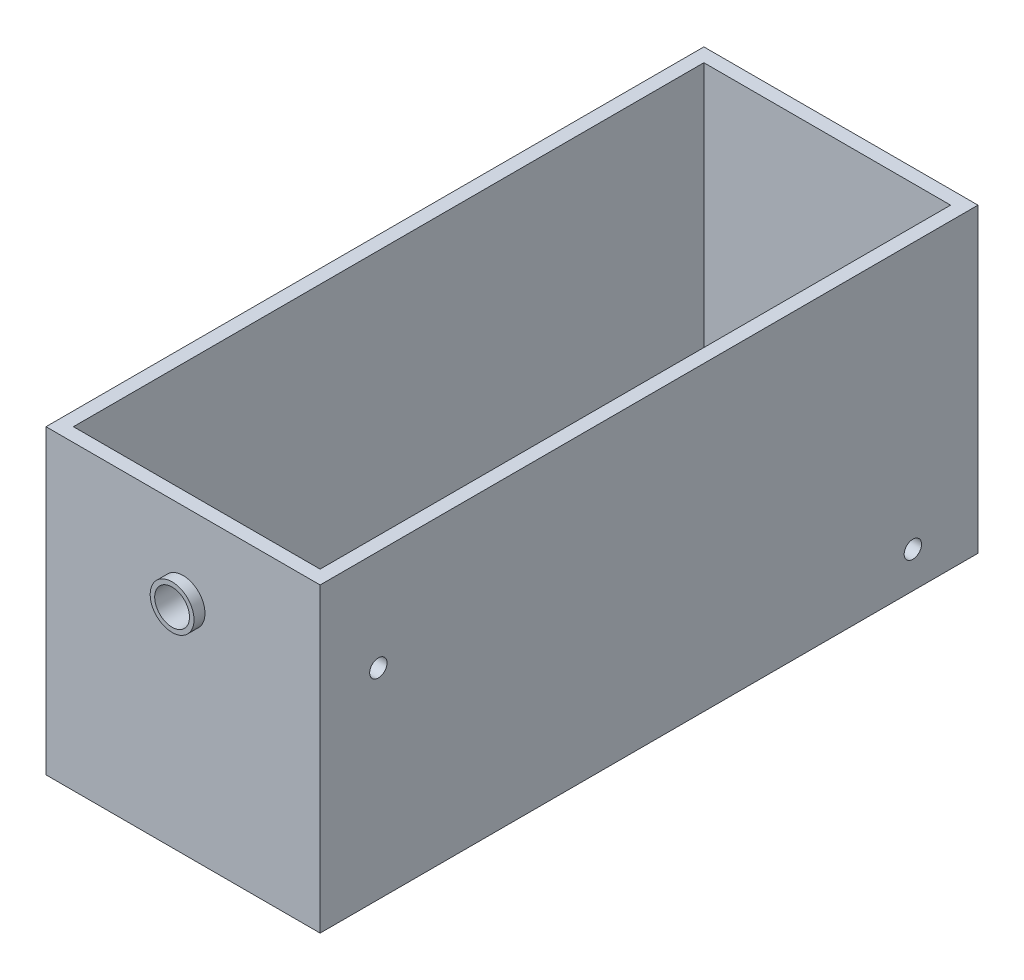
SolidWorks part; units mm, degrees
ref_plane "Front Plane" through (0, 0, 0) normal (0, 0, 1) x (1, 0, 0)
ref_plane "Top Plane" through (0, 0, 0) normal (0, 1, 0) x (1, 0, 0)
ref_plane "Right Plane" through (0, 0, 0) normal (1, 0, 0) x (0, 0, -1)
sketch "Sketch1" plane through (0, 0, 0) normal (0, 1, 0) x (1, 0, 0)
  line L1 (-25, -60) -> (25, -60)
  line L2 (-25, -60) -> (-25, 60)
  line L3 (-25, 60) -> (25, 60)
  line L4 (25, -60) -> (25, 60)
  line L5 (-25, -60) -> (25, 60) construction
  line L6 (-25, 60) -> (25, -60) construction
  point P0 (0, 0)
  dimension "D1" = 120
  dimension "D2" = 50
extrude "Boss-Extrude1" add sketch "Sketch1" along normal blind 5
sketch "Sketch2" plane through (0, 5, 0) normal (0, 1, 0) x (1, 0, 0)
  line L1 (-22.5, -57.5) -> (22.5, -57.5)
  line L2 (-22.5, -57.5) -> (-22.5, 57.5)
  line L3 (-22.5, 57.5) -> (22.5, 57.5)
  line L4 (22.5, -57.5) -> (22.5, 57.5)
  line L5 (-22.5, -57.5) -> (22.5, 57.5) construction
  line L6 (-22.5, 57.5) -> (22.5, -57.5) construction
  line L7 (-25, 60) -> (25, 60)
  line L8 (-25, 60) -> (-25, -60)
  line L9 (-25, -60) -> (25, -60)
  line L10 (25, 60) -> (25, -60)
  line L11 (-25, 60) -> (25, -60) construction
  line L12 (-25, -60) -> (25, 60) construction
  point P0 (0, 0)
  point P6 (0, 0)
  dimension "D1" = 45
  dimension "D2" = 115
extrude "Boss-Extrude2" add sketch "Sketch2" along normal blind 50
sketch "Sketch3" plane through (0, 0, 60) normal (0, 0, 1) x (1, 0, 0)
  line L0 (-25, 55) -> (25, 55) construction
  circle A0 centre (0, 40) radius 3.175
  dimension "D2" = 6.35
  dimension "D1" = 15
extrude "Cut-Extrude1" cut sketch "Sketch3" against normal blind 50
sketch "Sketch4" plane through (0, 0, 60) normal (0, 0, 1) x (1, 0, 0)
  circle A0 centre (0, 40) radius 3.175
  circle A1 centre (0, 40) radius 4
  dimension "D1" = 8
extrude "Boss-Extrude3" add sketch "Sketch4" along normal blind 2
sketch "Sketch5" plane through (0, 0, -60) normal (0, 0, -1) x (-1, 0, 0)
  line L0 (-25, 0) -> (25, 0) construction
  circle A0 centre (0, 10) radius 3.175
  dimension "D2" = 6.35
  dimension "D1" = 10
extrude "Cut-Extrude2" cut sketch "Sketch5" against normal blind 14
sketch "Sketch6" plane through (0, 0, -60) normal (0, 0, -1) x (-1, 0, 0)
  circle A0 centre (0, 10) radius 3.175
  circle A1 centre (0, 10) radius 4
  dimension "D1" = 8
extrude "Boss-Extrude4" add sketch "Sketch6" along normal blind 2
sketch "Sketch7" plane through (25, 0, 0) normal (1, 0, 0) x (0, 0, -1)
  circle A0 centre (-49.3768, 36.5849) radius 1.5875
  circle A1 centre (48.1207, 6.585) radius 1.585
extrude "Cut-Extrude3" cut sketch "Sketch7" against normal blind 10
